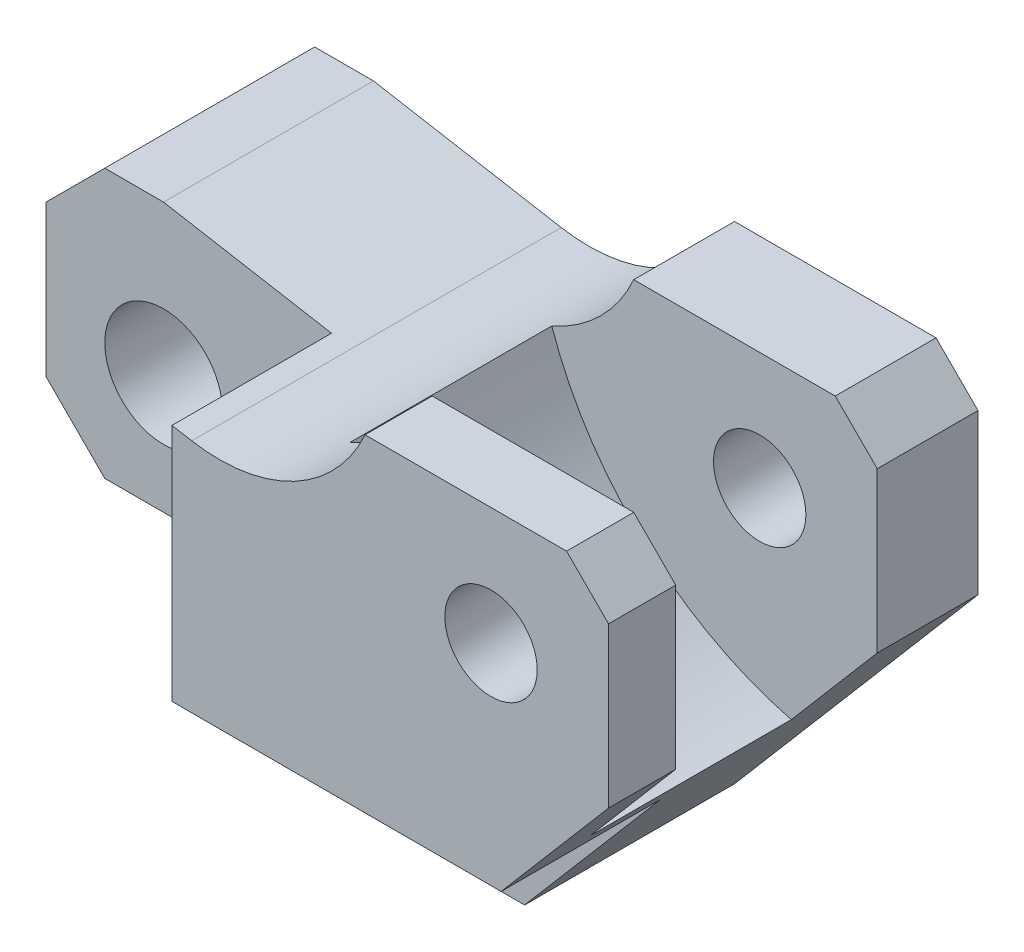
SolidWorks part; units mm, degrees
material "AISI 1020"
ref_plane "Front Plane" through (0, 0, 0) normal (0, 0, 1) x (1, 0, 0)
ref_plane "Top Plane" through (0, 0, 0) normal (0, 1, 0) x (1, 0, 0)
ref_plane "Right Plane" through (0, 0, 0) normal (1, 0, 0) x (0, 0, -1)
sketch "Sketch1" plane through (0, 0, 0) normal (0, 0, 1) x (1, 0, 0)
  line L0 (0, 0) -> (29, 34)
  line L1 (29, 34) -> (29, 53)
  line L2 (24, 58) -> (0, 58)
  line L3 (0, 0) -> (-5.703, 0)
  line L4 (-17.4245, 19) -> (-50, 19)
  line L5 (-57, 26) -> (-57, 44)
  line L6 (-50, 51) -> (-43, 51)
  line L7 (-43, 51) -> (-20.6386, 47.0571)
  line L8 (-57, 44) -> (-50, 51)
  line L9 (-50, 19) -> (-57, 26)
  line L10 (29, 53) -> (24, 58)
  line L11 (-43, 79.7238) -> (-43, -11.9481) construction
  line L12 (-76.1604, 33) -> (-11.9877, 33) construction
  line L13 (-23, 47.4735) -> (-23, 19)
  line L14 (16.2059, 19) -> (-23, 19)
  arc A0 (-12.4788, 14.7353) -> (-5.703, 0) centre (16.2059, 19) ccw
  arc A1 (-12.4788, 14.7353) -> (-17.4245, 19) centre (-17.4245, 14) ccw
  arc A2 (-20.6386, 47.0571) -> (0, 58) centre (-17.3393, 65.7684) ccw
  circle A3 centre (-43, 33) radius 7
  arc A4 (-9.7631, 48.3443) -> (18.7647, 22) centre (29, 61.7019) ccw
  circle A5 centre (15, 44) radius 5.5
  point P4 (29, 58)
  point P6 (16.2059, 19)
  point P10 (-57, 19)
  point P12 (-57, 51)
  point P29 (18.7647, 22)
  dimension "D6" = 29
  dimension "D7" = 5
  dimension "D13" = 19
  dimension "D22" = 14
  dimension "D25" = 41
  dimension "D28" = 11
  dimension "D1" = 29
  dimension "D2" = 24
  dimension "D3" = 58
  dimension "D4" = 29
  dimension "D5" = 19
  dimension "D8" = 86
  dimension "D9" = 19
  dimension "D10" = 32
  dimension "D11" = 14
  dimension "D12" = 10
  dimension "D14" = 7
  dimension "D15" = 45
  dimension "D16" = 7
  dimension "D17" = 45
  dimension "D18" = 5
  dimension "D19" = 45
  dimension "D20" = 14
  dimension "D21" = 14
  dimension "D23" = 52
  dimension "D24" = 36
  dimension "D26" = 14
  dimension "D27" = 14
extrude "Boss-Extrude1" add sketch "Sketch1" against normal blind 44 contours L8 L6 L7 A2 L2 L10 L1 L0 L3 A0 A1 L4 L9 L5 | A3
extrude "Cut-Extrude1" cut sketch "Sketch1<5>" against normal blind 19 contours L13 L7 L6 L8 L5 L9 L4 A3 | A1 A0 L3 L0 L14 region at (-0.9101, 11.5361, 0) region at (-36.5, 19.4669, 0)
sketch "Sketch1<5>" plane through (0, 0, 0) normal (0, 0, 1) x (1, 0, 0) same geometry as "Sketch1"
extrude "Cut-Extrude2" cut sketch "Sketch1<6>" against normal through all contours A5 region at (15, 44, 0)
sketch "Sketch1<6>" plane through (0, 0, 0) normal (0, 0, 1) x (1, 0, 0) same geometry as "Sketch1"
extrude "Cut-Extrude3" cut sketch "Sketch1<7>" against normal blind 24 from offset 8 contours A2 A4 L0 L1 L10 L2 A5 region at (1.5432, 31.9694, 0) offset against normal yes
sketch "Sketch1<7>" plane through (0, 0, 0) normal (0, 0, 1) x (1, 0, 0) same geometry as "Sketch1"
